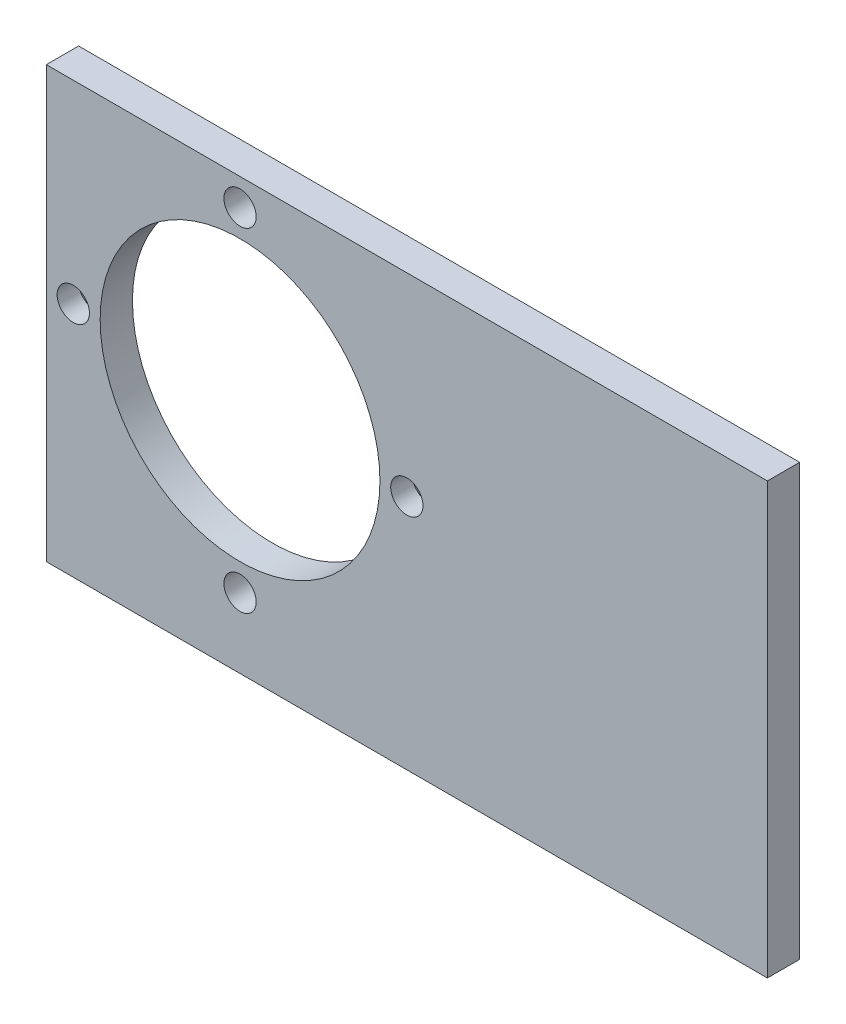
SolidWorks part; units mm, degrees
ref_plane "Front Plane" through (0, 0, 0) normal (0, 0, 1) x (1, 0, 0)
ref_plane "Top Plane" through (0, 0, 0) normal (0, 1, 0) x (1, 0, 0)
ref_plane "Right Plane" through (0, 0, 0) normal (1, 0, 0) x (0, 0, -1)
sketch "Sketch1" plane through (0, 0, 0) normal (0, 0, 1) x (1, 0, 0)
  line L0 (36.798, 101.1427) -> (103.7813, 99.6461) construction
  line L1 (36.9, 127.33) -> (103.9, 127.33) construction
  line L2 (36.9, 147.33) -> (103.9, 147.33)
  line L3 (36.9, 147.33) -> (36.9, 107.33)
  line L4 (36.9, 107.33) -> (103.9, 107.33)
  line L5 (103.9, 147.33) -> (103.9, 107.33)
  line L6 (41.9, 129.33) -> (67.9, 129.33) construction
  circle A0 centre (54.9, 129.33) radius 13
  circle A1 centre (54.9, 129.33) radius 15.5 construction
  circle A2 centre (39.4, 129.33) radius 1.5
  circle A3 centre (54.9, 144.83) radius 1.5
  circle A4 centre (70.4, 129.33) radius 1.5
  circle A5 centre (54.9, 113.83) radius 1.5
  point P25 (54.9, 129.33)
  dimension "D4" = 26
  dimension "D9" = 31
  dimension "D10" = 3
  dimension "D12" = 15.5
  dimension "D1" = 67
  dimension "D2" = 67
  dimension "D3" = 40
  dimension "D5" = 18
  dimension "D6" = 18
  dimension "D7" = 36.9
  dimension "D8" = 107.33
  dimension "D11" = 4
extrude "Boss-Extrude1" add sketch "Sketch1" along normal blind 3
chamfer "Chamfer1" distance 1 angle 45 2 edges at (40.9, 129.33, 0) (71.9, 129.33, 0)
